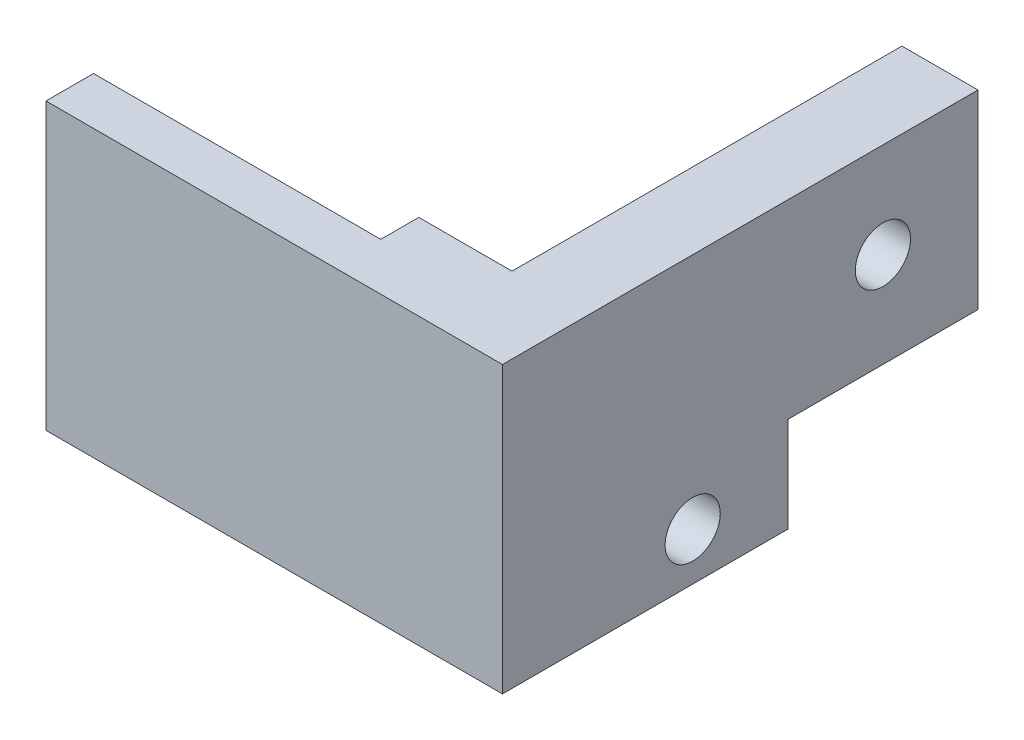
SolidWorks part; units mm, degrees
ref_plane "前视基准面" through (0, 0, 0) normal (0, 0, 1) x (1, 0, 0)
ref_plane "上视基准面" through (0, 0, 0) normal (0, 1, 0) x (1, 0, 0)
ref_plane "右视基准面" through (0, 0, 0) normal (1, 0, 0) x (0, 0, -1)
other "Configuration Table"
sketch "草图1" plane through (0, 0, 0) normal (0, 0, 1) x (1, 0, 0)
  line L1 (0, 0) -> (-40, 0)
  line L2 (0, 0) -> (0, 30)
  line L3 (0, 30) -> (-40, 30)
  line L4 (-40, 0) -> (-40, 30)
  dimension "D1" = 40
  dimension "D2" = 30
extrude "凸台-拉伸1" add sketch "草图1" along normal blind 5
sketch "草图2" plane through (-40, 0, 0) normal (-1, 0, 0) x (0, 0, 1)
  line L4 (0, 30) -> (0, 0)
  line L5 (0, 0) -> (5, 0)
  line L6 (5, 0) -> (5, 30)
  line L7 (5, 30) -> (0, 30)
  line L8 (0, 30) -> (0, 0)
  line L9 (0, 0) -> (5, 0)
  line L10 (5, 0) -> (5, 30)
  line L11 (5, 30) -> (0, 30)
  dimension "D1" = 0
extrude "凸台-拉伸2" add sketch "草图2" along normal blind 20
sketch "草图3" plane through (0, 0, 0) normal (0, 0, -1) x (-1, 0, 0)
  line L0 (60, 0) -> (0, 0) construction
  line L1 (60, 30) -> (40, 30) construction
  line L2 (60, 30) -> (60, 0) construction
  line L3 (60, 0) -> (40, 0) construction
  line L4 (40, 30) -> (40, 0) construction
  line L5 (30, 30) -> (30, 0) construction
  line L6 (0, 30) -> (60, 30) construction
  line L7 (0, 0) -> (20, 0)
  line L8 (20, 30) -> (20, 0)
  line L9 (0, 30) -> (20, 30)
  line L10 (0, 30) -> (0, 0)
  dimension "D1" = 20
extrude "凸台-拉伸3" add sketch "草图3" along normal blind 5
sketch "草图4" plane through (0, 0, 5) normal (0, 0, 1) x (1, 0, 0)
  line L0 (0, 30) -> (-60, 30) construction
  line L1 (-60, 30) -> (-45, 30) construction
  line L2 (-60, 30) -> (-60, 0) construction
  line L3 (-60, 0) -> (-45, 0) construction
  line L4 (-45, 30) -> (-45, 0) construction
  line L5 (-60, 0) -> (0, 0) construction
  line L6 (-60, 0) -> (-60, 30) construction
  line L7 (-30, 30) -> (-30, -4.6416) construction
  line L8 (0, 0) -> (-15, 0)
  line L9 (-15, 30) -> (-15, 0)
  line L10 (0, 30) -> (-15, 30)
  line L11 (0, 30) -> (0, 0)
  dimension "D1" = 0
  dimension "D2" = 15
extrude "切除-拉伸1" cut sketch "草图4" against normal blind 5
sketch "草图6" plane through (0, 0, 0) normal (0, 0, 1) x (1, 0, 0)
  line L0 (-7.5, 30) -> (-7.5, 25) construction
  line L1 (0, 30) -> (-15, 30) construction
  line L2 (-7.5, 25) -> (-7.5, 5) construction
  circle A0 centre (-7.5, 25) radius 1.5
  circle A1 centre (-7.5, 5) radius 1.5
  dimension "D3" = 3
  dimension "D4" = 3
  dimension "D1" = 5
  dimension "D2" = 20
extrude "切除-拉伸3" cut sketch "草图6" against normal blind 5
sketch "草图7" plane through (0, 0, 0) normal (0, 0, 1) x (1, 0, 0)
  line L4 (0, 0) -> (0, 30)
  line L5 (0, 30) -> (-15, 30)
  line L6 (-15, 30) -> (-15, 0)
  line L7 (-15, 0) -> (0, 0)
  line L8 (0, 0) -> (0, 30)
  line L9 (0, 30) -> (-15, 30)
  line L10 (-15, 30) -> (-15, 0)
  line L11 (-15, 0) -> (0, 0)
  dimension "D1" = 0
extrude "切除-拉伸4" cut sketch "草图7" against normal up to surface (5 mm away) up to face at (-6, 25, -5)
sketch "草图8" plane through (0, 0, -5) normal (0, 0, -1) x (-1, 0, 0)
  line L4 (15, 30) -> (15, 0)
  line L5 (15, 0) -> (20, 0)
  line L6 (20, 0) -> (20, 30)
  line L7 (20, 30) -> (15, 30)
  line L8 (15, 30) -> (15, 0)
  line L9 (15, 0) -> (20, 0)
  line L10 (20, 0) -> (20, 30)
  line L11 (20, 30) -> (15, 30)
  dimension "D1" = 0
extrude "凸台-拉伸4" add sketch "草图8" along normal blind 20
sketch "草图9" plane through (-15, 0, 0) normal (1, 0, 0) x (0, 0, -1)
  line L4 (-5, 30) -> (-5, 0)
  line L5 (-5, 0) -> (25, 0)
  line L6 (25, 0) -> (25, 30)
  line L7 (25, 30) -> (-5, 30)
  line L8 (-5, 30) -> (-5, 0)
  line L9 (-5, 0) -> (25, 0)
  line L10 (25, 0) -> (25, 30)
  line L11 (25, 30) -> (-5, 30)
  dimension "D1" = 0
extrude "凸台-拉伸5" add sketch "草图9" along normal blind 3
sketch "草图10" plane through (-12, 0, 0) normal (1, 0, 0) x (0, 0, -1)
  line L0 (25, 30) -> (15, 30) construction
  line L1 (25, 30) -> (-5, 30) construction
  line L2 (15, 30) -> (15, 5) construction
  circle A0 centre (15, 5) radius 1.5
  dimension "D3" = 3
  dimension "D1" = 10
  dimension "D2" = 25
extrude "切除-拉伸5" cut sketch "草图10" against normal blind 13
sketch "草图11" plane through (-12, 0, 0) normal (1, 0, 0) x (0, 0, -1)
  circle A0 centre (15, 5) radius 2.9
  dimension "D1" = 5.8
extrude "切除-拉伸6" cut sketch "草图11" against normal offset from surface (6 mm away) 2 up to face at (-20, 5, -16.5)
sketch "草图12" plane through (0, 0, -25) normal (0, 0, -1) x (-1, 0, 0)
  line L1 (20, 30) -> (12, 30)
  line L2 (20, 30) -> (20, 10)
  line L3 (20, 10) -> (12, 10)
  line L4 (12, 30) -> (12, 10)
  dimension "D1" = 20
extrude "凸台-拉伸6" add sketch "草图12" along normal blind 20
sketch "草图13" plane through (-20, 0, 0) normal (-1, 0, 0) x (0, 0, 1)
  line L0 (-45, 10) -> (-45, 30) construction
  line L1 (-45, 17) -> (-25, 17)
  line L2 (-45, 17) -> (-45, 10)
  line L3 (-45, 10) -> (-25, 10)
  line L6 (-25, 0) -> (-18, 0)
  line L7 (-25, 0) -> (-25, 10)
  line L8 (-25, 17) -> (-18, 17)
  line L9 (-18, 0) -> (-18, 17)
  dimension "D1" = 7
  dimension "D2" = 7
extrude "切除-拉伸7" cut sketch "草图13" against normal blind 4.2
sketch "草图14" plane through (-12, 0, 0) normal (1, 0, 0) x (0, 0, -1)
  line L0 (45, 30) -> (45, 20) construction
  line L1 (45, 30) -> (45, 10) construction
  line L2 (45, 20) -> (35, 20) construction
  circle A0 centre (35, 20) radius 1.5
  dimension "D2" = 3
  dimension "D1" = 10
extrude "切除-拉伸8" cut sketch "草图14" against normal blind 14.2
sketch "草图15" plane through (-12, 0, 0) normal (1, 0, 0) x (0, 0, -1)
  circle A0 centre (35, 20) radius 2.9
  dimension "D1" = 5.8
extrude "切除-拉伸9" cut sketch "草图15" against normal offset from surface (6 mm away) 2 up to face at (-20, 20, -36.5)
sketch "草图16" plane through (-20, 0, 0) normal (-1, 0, 0) x (0, 0, 1)
  line L0 (-18, 0) -> (0, 0) construction
  line L1 (0, 30) -> (-4, 30)
  line L2 (0, 30) -> (0, 0)
  line L3 (0, 0) -> (-4, 0)
  line L4 (-4, 30) -> (-4, 0)
  dimension "D1" = 4
extrude "凸台-拉伸7" add sketch "草图16" along normal blind 9.8
